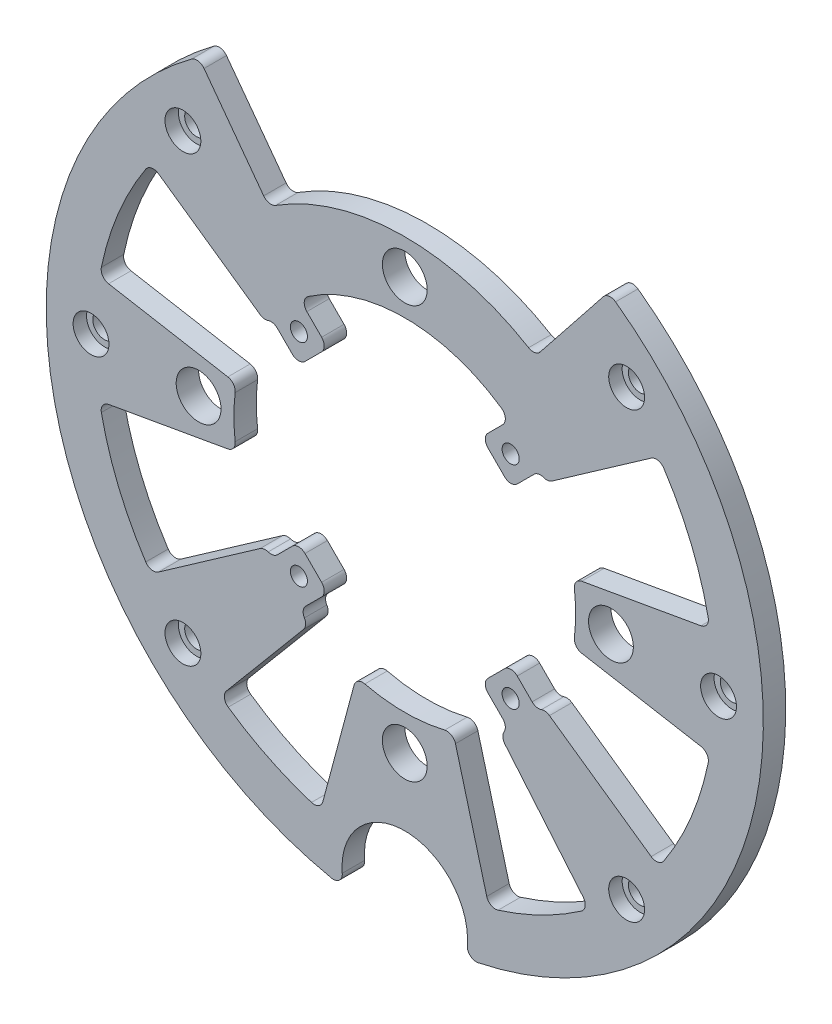
SolidWorks part; units mm, degrees
ref_plane "Front Plane" through (0, 0, 0) normal (0, 0, 1) x (1, 0, 0)
ref_plane "Top Plane" through (0, 0, 0) normal (0, 1, 0) x (1, 0, 0)
ref_plane "Right Plane" through (0, 0, 0) normal (1, 0, 0) x (0, 0, -1)
sketch "Sketch1" plane through (0, 0, 0) normal (0, 0, 1) x (1, 0, 0)
  circle A0 centre (0, 0) radius 48.4359
  circle A1 centre (0, 0) radius 101.6
extrude "Extrude1" add sketch "Sketch1" along normal blind 6.35
sketch "Sketch4" plane through (0, 0, 6.35) normal (0, 0, 1) x (1, 0, 0)
  point P0 (62.8618, -62.8618)
  point P1 (88.9, 0)
  point P2 (62.8618, 62.8618)
  point P3 (-62.8618, 62.8618)
  point P4 (-88.9, 0)
  point P5 (-62.8618, -62.8618)
hole_wizard "CBORE for 1/4 Socket Head Cap Screw1" positions "Sketch9" profile "Sketch8" counterbore size "1/4" standard "Ansi Inch" end condition through all
sketch "Sketch9" plane through (0, 0, 6.35) normal (0, 0, 1) x (1, 0, 0)
  point P1 (62.8618, -62.8618)
  point P3 (88.9, 0)
  point P5 (62.8618, 62.8618)
  point P7 (-62.8618, 62.8618)
  point P9 (-88.9, 0)
  point P11 (-62.8618, -62.8618)
sketch "Sketch8" plane through (62.8618, -62.8618, 6.35) normal (1, 0, 0) x (0, -1, 0)
  line L0 (0, 0) -> (0, 6.35)
  line L1 (0, 6.35) -> (3.3147, 6.35)
  line L3 (3.3147, 6.35) -> (3.3147, 3.81)
  line L4 (3.3147, 3.81) -> (5.08, 3.81)
  line L5 (5.08, 3.81) -> (5.08, 0)
  line L7 (5.08, 0) -> (0, 0)
  line L11 (0, -6.35) -> (0, 107.95) construction
  dimension "Thru Hole Dia." = 6.6294
  dimension "Thru Hole Depth" = 6.35
  dimension "C'Bore Dia." = 10.16
  dimension "C'Bore Depth" = 3.81
sketch "Sketch11" plane through (0, 0, 6.35) normal (0, 0, 1) x (1, 0, 0)
  circle A0 centre (0, -95.25) radius 17.78
extrude "Cut-Extrude1" cut sketch "Sketch11" against normal through all
sketch "Sketch12" plane through (0, 0, 6.35) normal (0, 0, 1) x (1, 0, 0)
  line L0 (-58.42, 0) -> (58.42, 0) construction
  circle A0 centre (0, -58.42) radius 6.35
  circle A1 centre (-58.42, 0) radius 6.35
  circle A2 centre (58.42, 0) radius 6.35
  circle A3 centre (0, 58.42) radius 6.35
  dimension "D1" = 12.7
extrude "Cut-Extrude2" cut sketch "Sketch12" against normal through all
sketch "Sketch13" plane through (0, 0, 6.35) normal (0, 0, 1) x (1, 0, 0)
  line L0 (0, 0) -> (0, -67.9248) construction
  line L1 (0, 0) -> (61.5438, 0) construction
  line L2 (0, 0) -> (29.9999, -29.9999) construction
  line L3 (30.0672, -21.7618) -> (44.904, -36.5986)
  line L4 (44.904, -36.5986) -> (36.5986, -44.904)
  line L5 (30.0672, -21.7618) -> (21.7618, -30.0672)
  line L6 (21.7618, -30.0672) -> (36.5986, -44.904)
  line L7 (-30.0672, -21.7618) -> (-44.904, -36.5986)
  line L8 (-30.0672, -21.7618) -> (-21.7618, -30.0672)
  line L9 (-21.7618, -30.0672) -> (-36.5986, -44.904)
  line L10 (-44.904, -36.5986) -> (-36.5986, -44.904)
  line L11 (-30.0672, 21.7618) -> (-21.7618, 30.0672)
  line L12 (-30.0672, 21.7618) -> (-44.904, 36.5986)
  line L13 (-44.904, 36.5986) -> (-36.5986, 44.904)
  line L14 (-21.7618, 30.0672) -> (-36.5986, 44.904)
  line L15 (30.0672, 21.7618) -> (21.7618, 30.0672)
  line L16 (30.0672, 21.7618) -> (44.904, 36.5986)
  line L17 (21.7618, 30.0672) -> (36.5986, 44.904)
  line L18 (44.904, 36.5986) -> (36.5986, 44.904)
  circle A0 centre (-29.9999, 29.9999) radius 2.4265
  circle A1 centre (29.9999, 29.9999) radius 2.4265
  circle A2 centre (-29.9999, -29.9999) radius 2.4265
  circle A3 centre (29.9999, -29.9999) radius 2.4265
  point P11 (25.9145, -25.9145)
  point P12 (40.7513, -40.7513)
extrude "Extrude2" add sketch "Sketch13" against normal up to surface (6.35 mm away) up to face at (-6.35, 58.42, 0)
sketch "Sketch14" plane through (0, 0, 6.35) normal (0, 0, 1) x (1, 0, 0)
  line L0 (0, -7.6401) -> (0, -64.3895) construction
  line L1 (0, 0) -> (76.0963, 0) construction
  line L2 (36.9784, 57.4547) -> (71.6833, 101.141)
  line L3 (71.6833, 101.141) -> (0, 148.4755)
  line L4 (-71.6833, 101.141) -> (0, 148.4755)
  line L5 (-38.5448, 56.4158) -> (-71.6833, 101.141)
  line L6 (8.6526, -27.5809) -> (23.9004, -84.4864)
  line L7 (14.2276, -25.1624) -> (52.2951, -70.5294)
  line L8 (-71.9231, 50.3611) -> (-23.6786, 16.5799)
  line L9 (-86.468, 15.2466) -> (-28.4671, 5.0195)
  line L10 (-8.6522, -27.581) -> (-23.9004, -84.4864)
  line L11 (-14.2295, -25.1613) -> (-52.2951, -70.5294)
  line L12 (-86.468, -15.2466) -> (-28.4671, -5.0195)
  line L13 (-71.9231, -50.3611) -> (-23.6786, -16.5799)
  line L14 (23.6786, -16.5799) -> (71.9231, -50.3611)
  line L15 (28.4671, -5.0195) -> (86.468, -15.2466)
  line L16 (28.4671, 5.0195) -> (86.468, 15.2466)
  line L17 (23.6786, 16.5799) -> (71.9231, 50.3611)
  arc A0 (23.9004, -84.4864) -> (52.2951, -70.5294) centre (0, 0) ccw
  arc A1 (-52.2951, -70.5294) -> (-23.9004, -84.4864) centre (0, 0) ccw
  arc A2 (-86.468, -15.2466) -> (-71.9231, -50.3611) centre (0, 0) ccw
  arc A3 (-71.9231, 50.3611) -> (-86.468, 15.2466) centre (0, 0) ccw
  arc A4 (86.468, 15.2466) -> (71.9231, 50.3611) centre (0, 0) ccw
  arc A5 (71.9231, -50.3611) -> (86.468, -15.2466) centre (0, 0) ccw
  arc A6 (36.9784, 57.4547) -> (-38.5448, 56.4158) centre (0, 0) ccw
  arc A7 (28.4671, 5.0195) -> (23.6786, 16.5799) centre (0, 0) ccw
  arc A8 (23.6786, -16.5799) -> (28.4671, -5.0195) centre (0, 0) ccw
  arc A9 (8.6526, -27.5809) -> (14.2276, -25.1624) centre (0, 0) ccw
  arc A10 (-14.2295, -25.1613) -> (-8.6522, -27.581) centre (0, 0) ccw
  arc A11 (-28.4671, -5.0195) -> (-23.6786, -16.5799) centre (0, 0) ccw
  arc A12 (-23.6786, 16.5799) -> (-28.4671, 5.0195) centre (0, 0) ccw
  dimension "D5" = 75
  dimension "D1" = 10
  dimension "D2" = 15
  dimension "D3" = 25
  dimension "D4" = 25
extrude "Cut-Extrude3" cut sketch "Sketch14" against normal blind 6.35
fillet "Fillet1" radius 2.54 23 edges at (47.7, -8.4108, 3.175) (29.8439, -38.1494, 3.175) (-58.3635, 83.164, 3.175) (-30.0672, -21.7618, 3.175) (-30.0672, 21.7618, 3.175) (30.0672, 21.7618, 3.175) (-21.7618, -30.0672, 3.175) (-21.7618, 30.0672, 3.175) (21.7618, -30.0672, 3.175) (30.0672, -21.7618, 3.175) (21.7618, 30.0672, 3.175) (86.468, 15.2466, 3.175) (71.9231, 50.3611, 3.175) (-86.468, -15.2466, 3.175) (23.9004, -84.4864, 3.175) (52.2951, -70.5294, 3.175) (-71.9231, 50.3611, 3.175) (86.468, -15.2466, 3.175) (-71.9231, -50.3611, 3.175) (71.9231, -50.3611, 3.175) (-23.9004, -84.4864, 3.175) (-52.2951, -70.5294, 3.175) (-86.468, 15.2466, 3.175)
fillet "Fillet2" radius 2.54 2 edges at (-38.1494, -29.8439, 3.175) (39.6763, 27.7817, 3.175)
fillet "Fillet3" radius 2.54 4 edges at (38.1494, -29.8439, 3.175) (26.9079, -40.2741, 3.175) (13.71, -46.455, 3.175) (-29.8439, 38.1494, 3.175)
fillet "Fillet4" radius 2.54 6 edges at (-38.1494, 29.8439, 3.175) (-47.7, -8.4108, 3.175) (17.0908, -100.1522, 3.175) (47.7, 8.4108, 3.175) (39.6763, -27.7817, 3.175) (57.7446, 83.595, 3.175)
fillet "Fillet5" radius 2.54 5 edges at (-39.6763, 27.7817, 3.175) (-47.7, 8.4108, 3.175) (-26.9091, -40.2733, 3.175) (-17.0908, -100.1522, 3.175) (-13.7096, -46.4551, 3.175)
fillet "Fillet6" radius 2.54 4 edges at (-29.8439, -38.1494, 3.175) (-39.6763, -27.7817, 3.175) (38.1494, 29.8439, 3.175) (29.8439, 38.1494, 3.175)
fillet "Fillet9" radius 2.54 2 edges at (-38.5448, 56.4158, 3.175) (36.9784, 57.4547, 3.175)
